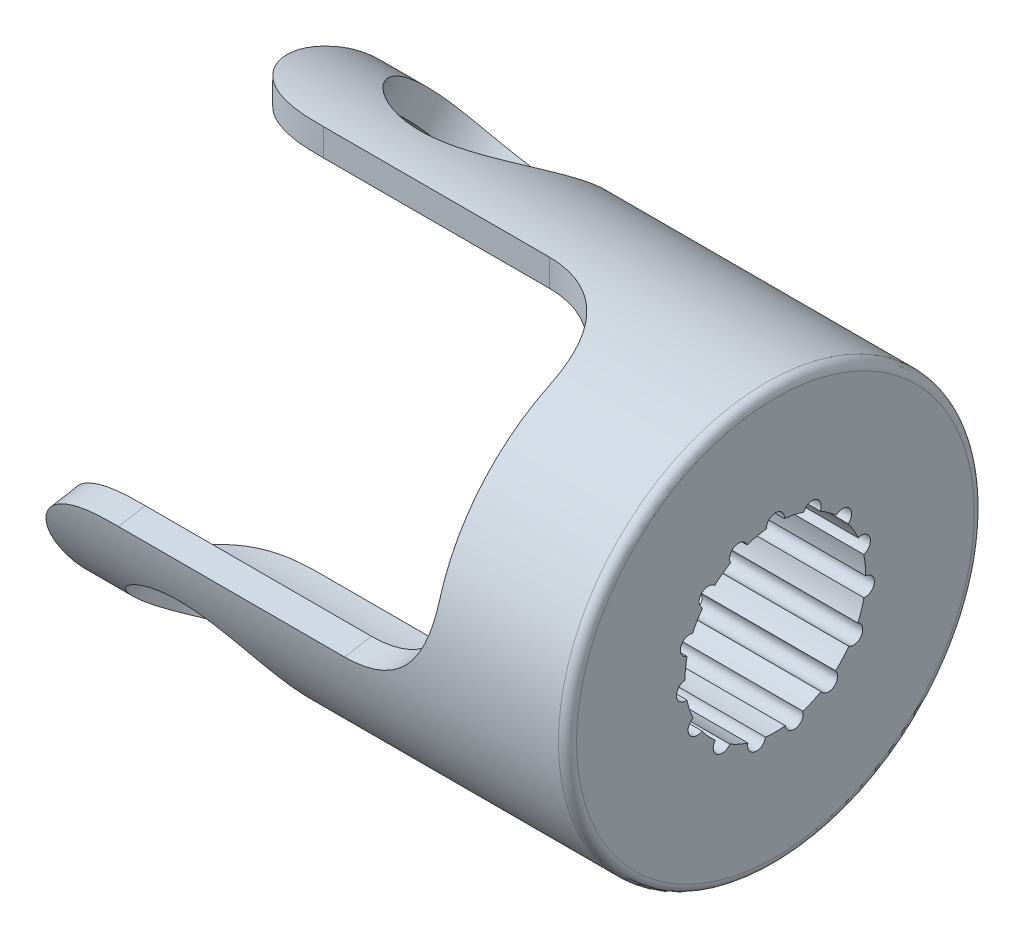
SolidWorks part; units mm, degrees
ref_plane "Front Plane" through (0, 0, 0) normal (0, 0, 1) x (1, 0, 0)
ref_plane "Top Plane" through (0, 0, 0) normal (0, 1, 0) x (1, 0, 0)
ref_plane "Right Plane" through (0, 0, 0) normal (1, 0, 0) x (0, 0, -1)
sketch "Sketch1" plane through (0, 0, 0) normal (0, 0, 1) x (1, 0, 0)
  line L0 (0, 20) -> (45, 20)
  line L1 (45, 20) -> (45, 0)
  line L2 (45, 0) -> (0, 0) construction
  line L3 (0, 20) -> (0, 23)
  line L4 (0, 23) -> (48, 23)
  line L5 (48, 23) -> (48, 0)
  line L6 (48, 0) -> (45, 0)
  dimension "D1" = 20
  dimension "D2" = 3
  dimension "D3" = 45
revolve "Revolve1" add sketch "Sketch1" angle 80 about L6
pattern_circular "CirPattern1" count 2 over 360 about axis through (48, 0, 0) along (1, 0, 0) reverse direction yes of bodies 101
sketch "Sketch3" plane through (48, 0, 0) normal (1, 0, 0) x (0, 0, -1)
  circle A0 centre (0, 0) radius 23
  arc A1 (22.6506, 3.9939) -> (0, 23) centre (0, 0) ccw construction
extrude "Boss-Extrude1" add sketch "Sketch3" against normal up to surface (3 mm away) up to face at (45, -9.0191, 7.5679)
fillet "Fillet3" radius 10 4 edges at (0, 3.7334, -21.1734) (0, 21.5, 0) (0, -3.7334, 21.1734) (0, -21.5, 0) curvature continuous yes
ref_axis "Axis1" through (-0.05, 0, 0) along (1, 0, 0)
ref_plane "Plane2" through (0, -17.619, 14.7841) normal (0, -0.766, 0.6428) x (1, 0, 0)
sketch "Sketch8" plane through (0, -17.619, 14.7841) normal (0, -0.766, 0.6428) x (1, 0, 0)
  line L0 (-0.05, 0) -> (48, 0) construction
  circle A0 centre (15, 0) radius 10
  dimension "D2" = 20
  dimension "D1" = 15
extrude "Cut-Extrude1" cut sketch "Sketch8" against normal through all
sketch "Sketch9" plane through (48, 0, 0) normal (1, 0, 0) x (0, 0, -1)
  circle A1 centre (0, 0) radius 23
  circle A2 centre (0, 0) radius 23
  dimension "D1" = 0
extrude "Boss-Extrude2" add sketch "Sketch9" along normal blind 12
fillet "Fillet7" radius 1 1 edges at (60, 23, 0)
ref_axis "Axis2" through (15, 39.2642, -32.9466) along (0, -0.766, 0.6428)
fillet "Fillet8" radius 10 4 edges at (45, 3.7334, -21.1734) (45, -21.5, 0) (45, -3.7334, 21.1734) (45, 21.5, 0)
ref_plane "Plane3" through (0, 0, 0) normal (0, -0.766, 0.6428) x (1, 0, 0)
sketch "Sketch13" plane through (60, 0, 0) normal (1, 0, 0) x (0, 0, -1)
  circle A0 centre (0, 0) radius 10
  dimension "D1" = 20
extrude "Cut-Extrude2" cut sketch "Sketch13" against normal up to next
sketch "Sketch14" plane through (60, 0, 0) normal (1, 0, 0) x (0, 0, -1)
  circle A0 centre (0, 10) radius 1
  circle A1 centre (0, 0) radius 10 construction
  dimension "D1" = 2
extrude "Cut-Extrude3" cut sketch "Sketch14" against normal up to next
pattern_circular "CirPattern2" count 15 over 360 about axis through (-0.05, 0, 0) along (1, 0, 0) of "Cut-Extrude3"
